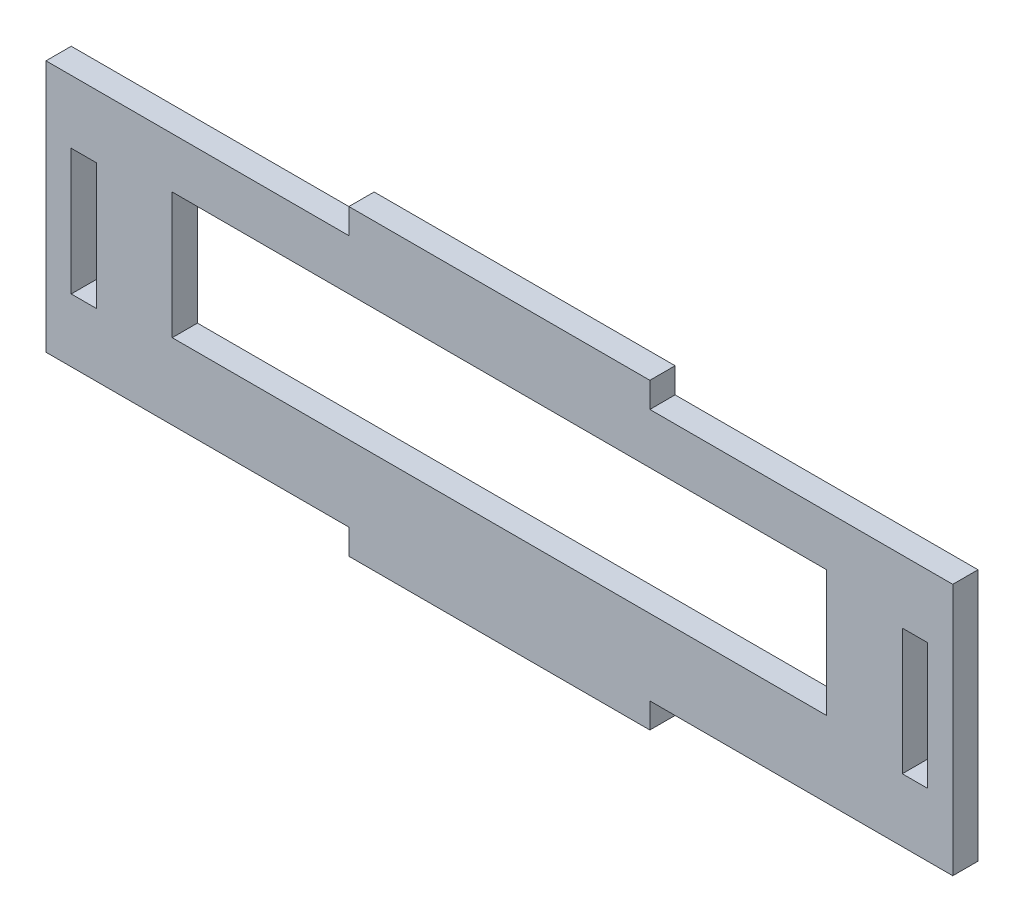
SolidWorks part; units mm, degrees
ref_plane "Front Plane" through (0, 0, 0) normal (0, 0, 1) x (1, 0, 0)
ref_plane "Top Plane" through (0, 0, 0) normal (0, 1, 0) x (1, 0, 0)
ref_plane "Right Plane" through (0, 0, 0) normal (1, 0, 0) x (0, 0, -1)
sketch "Sketch1" plane through (0, 0, 0) normal (0, 0, 1) x (1, 0, 0)
  line L0 (0, 0) -> (24, 0)
  line L2 (0, 0) -> (0, 20)
  line L4 (71.848, 0) -> (71.848, 20)
  line L5 (24, 0) -> (24, -2)
  line L6 (24, -2) -> (47.848, -2)
  line L7 (47.848, -2) -> (47.848, 0)
  line L8 (47.848, 0) -> (71.848, 0)
  line L9 (0, 20) -> (24, 20)
  line L10 (24, 20) -> (24, 22)
  line L11 (24, 22) -> (47.848, 22)
  line L12 (47.848, 22) -> (47.848, 20)
  line L13 (47.848, 20) -> (71.848, 20)
  line L15 (10, 6) -> (61.848, 6)
  line L16 (10, 6) -> (10, 16)
  line L17 (10, 16) -> (61.848, 16)
  line L18 (61.848, 6) -> (61.848, 16)
  line L19 (2, 15) -> (4, 15)
  line L20 (2, 15) -> (2, 5)
  line L21 (2, 5) -> (4, 5)
  line L22 (4, 15) -> (4, 5)
  line L23 (67.848, 15) -> (69.848, 15)
  line L24 (67.848, 15) -> (67.848, 5)
  line L25 (67.848, 5) -> (69.848, 5)
  line L26 (69.848, 15) -> (69.848, 5)
  dimension "D1" = 20
  dimension "D2" = 6
  dimension "D3" = 10
  dimension "D4" = 10
  dimension "D5" = 10
  dimension "D6" = 2
  dimension "D7" = 5
  dimension "D8" = 5
  dimension "D9" = 2
extrude "Boss-Extrude1" add sketch "Sketch1" along normal blind 2
